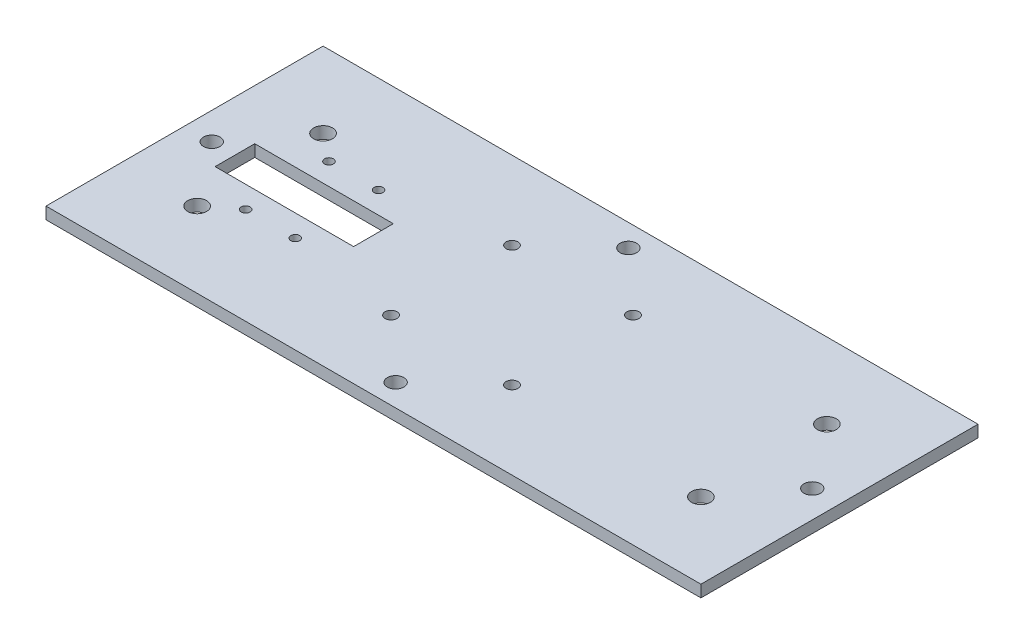
SolidWorks part; units mm, degrees
material "Thornel VCB-20 Carbon Cloth"
ref_plane "Front Plane" through (0, 0, 0) normal (0, 0, 1) x (1, 0, 0)
ref_plane "Top Plane" through (0, 0, 0) normal (0, 1, 0) x (1, 0, 0)
ref_plane "Right Plane" through (0, 0, 0) normal (1, 0, 0) x (0, 0, -1)
sketch "Sketch1" plane through (0, 0, 0) normal (0, 1, 0) x (1, 0, 0)
  line L0 (82.55, -34.925) -> (82.55, 34.925)
  line L1 (82.55, -34.925) -> (-82.55, -34.925)
  line L2 (82.55, 34.925) -> (-82.55, 34.925)
  line L3 (-82.55, -34.925) -> (-82.55, 34.925)
  line L4 (82.55, -34.925) -> (-82.55, 34.925) construction
  line L5 (82.55, 34.925) -> (-82.55, -34.925) construction
  point P1 (0, 0)
  dimension "D1" = 165.1
  dimension "D2" = 69.85
extrude "Boss-Extrude1" add sketch "Sketch1" along normal blind 3
sketch "Sketch6" plane through (0, 0, 0) normal (0, -1, 0) x (1, 0, 0)
  line L0 (-82.55, -34.925) -> (-82.55, 34.925) construction
  line L1 (-69.85, 5) -> (-34.925, 5)
  line L2 (-69.85, 5) -> (-69.85, -5)
  line L3 (-69.85, -5) -> (-34.925, -5)
  line L4 (-34.925, 5) -> (-34.925, -5)
  circle A0 centre (-15.25, 15.25) radius 1.5
  circle A1 centre (15.25, 15.25) radius 1.5
  circle A2 centre (-15.25, -15.25) radius 1.5
  circle A3 centre (15.25, -15.25) radius 1.5
  point P8 (-34.925, 0)
  dimension "D5" = 3
  dimension "D6" = 3
  dimension "D7" = 3
  dimension "D8" = 3
  dimension "D1" = 34.925
  dimension "D2" = 10
  dimension "D3" = 12.7
  dimension "D9" = 15.25
  dimension "D10" = 15.25
  dimension "D11" = 15.25
  dimension "D12" = 15.25
  dimension "D13" = 15.25
  dimension "D14" = 15.25
  dimension "D15" = 15.25
  dimension "D16" = 15.25
extrude "Cut-Extrude1" cut sketch "Sketch6" against normal up to next
sketch "Sketch7" plane through (0, 3, 0) normal (0, 1, 0) x (1, 0, 0)
  line L0 (-82.55, 34.925) -> (-82.55, -34.925) construction
  line L1 (82.55, -34.925) -> (82.55, 34.925) construction
  line L2 (-82.55, -34.925) -> (82.55, -34.925) construction
  line L3 (82.55, 34.925) -> (-82.55, 34.925) construction
  circle A0 centre (-77.47, 29.845) radius 1.5
  circle A1 centre (-77.47, -29.845) radius 1.5
  circle A2 centre (77.47, -29.845) radius 1.5
  circle A3 centre (77.47, 29.845) radius 1.5
  dimension "D9" = 3
  dimension "D10" = 3
  dimension "D11" = 3
  dimension "D12" = 3
  dimension "D1" = 5.08
  dimension "D2" = 5.08
  dimension "D3" = 5.08
  dimension "D4" = 5.08
  dimension "D5" = 5.08
  dimension "D6" = 5.08
  dimension "D7" = 5.08
  dimension "D8" = 5.08
sketch "Sketch8" plane through (0, 3, 0) normal (0, 1, 0) x (1, 0, 0)
  line L0 (-82.55, -34.925) -> (82.55, -34.925) construction
  line L1 (-82.55, 34.925) -> (-82.55, -34.925) construction
  line L2 (82.55, -34.925) -> (82.55, 34.925) construction
  line L3 (82.55, 34.925) -> (-82.55, 34.925) construction
  circle A0 centre (-63.5, -15.875) radius 2.3813
  circle A1 centre (-63.5, 15.875) radius 2.3813
  circle A2 centre (63.5, 15.875) radius 2.3813
  circle A3 centre (63.5, -15.875) radius 2.3813
  dimension "D1" = 4.7625
  dimension "D4" = 4.7625
  dimension "D5" = 4.7625
  dimension "D6" = 4.7625
  dimension "D2" = 19.05
  dimension "D3" = 19.05
  dimension "D7" = 19.05
  dimension "D8" = 19.05
  dimension "D9" = 19.05
  dimension "D10" = 19.05
  dimension "D11" = 19.05
  dimension "D12" = 19.05
extrude "Cut-Extrude3" cut sketch "Sketch8" against normal up to next
sketch "Sketch9" plane through (0, 3, 0) normal (0, 1, 0) x (1, 0, 0)
  line L0 (-82.55, 34.925) -> (-82.55, -34.925) construction
  line L1 (82.55, -34.925) -> (82.55, 34.925) construction
  circle A0 centre (-75.692, 0) radius 2.0828
  circle A1 centre (75.692, 0) radius 2.0828
  dimension "D1" = 6.858
  dimension "D2" = 6.858
extrude "Cut-Extrude5" cut sketch "Sketch9" against normal blind 5.08
sketch "Sketch10" plane through (0, 3, 0) normal (0, 1, 0) x (1, 0, 0)
  line L0 (-82.55, -34.925) -> (82.55, -34.925) construction
  line L1 (82.55, 34.925) -> (-82.55, 34.925) construction
  circle A0 centre (0, -29.337) radius 2.0828
  circle A1 centre (0, 29.337) radius 2.0828
  dimension "D1" = 5.588
  dimension "D2" = 5.588
extrude "Cut-Extrude6" cut sketch "Sketch10" against normal blind 5.08 contours A1 | A0
sketch "Sketch11" plane through (0, 3, 0) normal (0, 1, 0) x (1, 0, 0)
  line L1 (-44.1375, 10.5) -> (-56.6375, 10.5) construction
  line L2 (-44.1375, 10.5) -> (-44.1375, -10.5) construction
  line L3 (-44.1375, -10.5) -> (-56.6375, -10.5) construction
  line L4 (-56.6375, 10.5) -> (-56.6375, -10.5) construction
  line L5 (-44.1375, 10.5) -> (-56.6375, -10.5) construction
  line L6 (-44.1375, -10.5) -> (-56.6375, 10.5) construction
  line L7 (-34.925, 5) -> (-69.85, 5) construction
  circle A0 centre (-56.6375, 10.5) radius 1.125
  circle A1 centre (-44.1375, 10.5) radius 1.125
  circle A2 centre (-44.1375, -10.5) radius 1.125
  circle A3 centre (-56.6375, -10.5) radius 1.125
  point P0 (-50.3875, 0)
  point P9 (-52.3875, 5)
  dimension "D4" = 2.25
  dimension "D5" = 2.25
  dimension "D6" = 2.25
  dimension "D7" = 2.25
  dimension "D1" = 12.5
  dimension "D2" = 21
  dimension "D3" = 2
extrude "Cut-Extrude7" cut sketch "Sketch11" against normal blind 41.91
